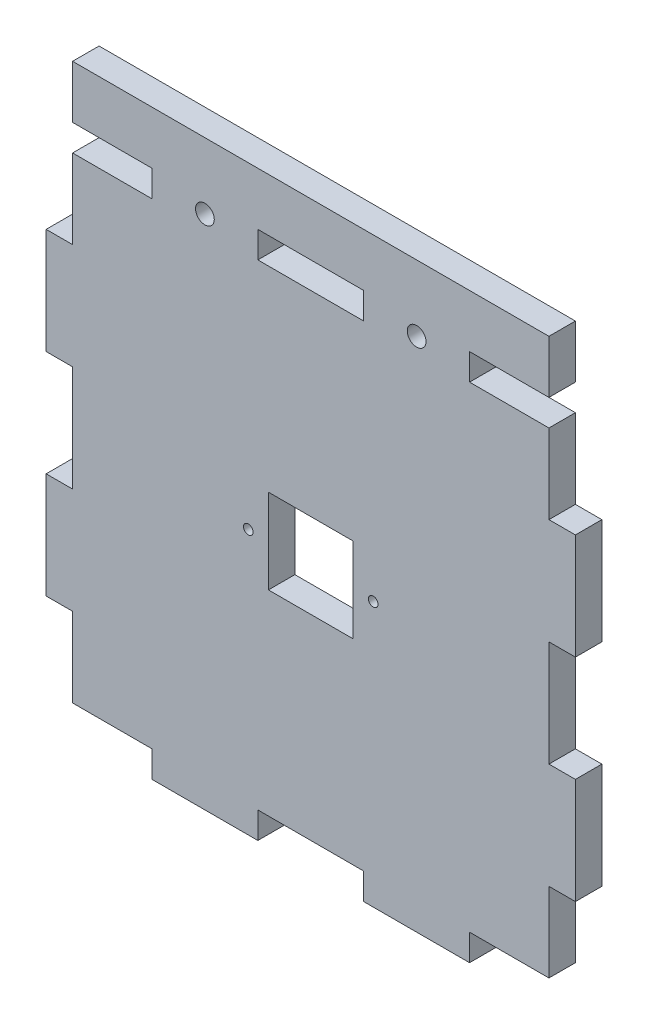
SolidWorks part; units mm, degrees
ref_plane "Front Plane" through (0, 0, 0) normal (0, 0, 1) x (1, 0, 0)
ref_plane "Top Plane" through (0, 0, 0) normal (0, 1, 0) x (1, 0, 0)
ref_plane "Right Plane" through (0, 0, 0) normal (1, 0, 0) x (0, 0, -1)
sketch "Sketch1" plane through (0, 0, 0) normal (0, 0, 1) x (1, 0, 0)
  line L1 (0, 0) -> (127, 0)
  line L2 (0, 0) -> (0, 139.7)
  line L3 (0, 139.7) -> (127, 139.7)
  line L4 (127, 0) -> (127, 139.7)
  dimension "D1" = 127
  dimension "D2" = 139.7
extrude "Boss-Extrude1" add sketch "Sketch1" along normal blind 6.35
sketch "Sketch5" plane through (0, 0, 6.35) normal (0, 0, 1) x (1, 0, 0)
  line L1 (0, 0) -> (6.35, 0)
  line L2 (0, 0) -> (0, 25.4)
  line L3 (0, 25.4) -> (6.35, 25.4)
  line L4 (6.35, 0) -> (6.35, 25.4)
  dimension "D1" = 25.4
  dimension "D2" = 6.35
extrude "Cut-Extrude4" cut sketch "Sketch5" against normal blind 6.35
sketch "Sketch6" plane through (0, 0, 6.35) normal (0, 0, 1) x (1, 0, 0)
  line L1 (0, 0) -> (25.4, 0)
  line L2 (0, 0) -> (0, 6.35)
  line L3 (0, 6.35) -> (25.4, 6.35)
  line L4 (25.4, 0) -> (25.4, 6.35)
  dimension "D1" = 6.35
  dimension "D2" = 25.4
extrude "Cut-Extrude5" cut sketch "Sketch6" against normal blind 6.35
pattern_linear "LPattern5" count 3 spacing 50.8 along (0, 1, 0) count 2 spacing 120.65 along (1, 0, 0) of "Cut-Extrude4"
pattern_linear "LPattern6" count 3 spacing 50.8 along (1, 0, 0) count 2 spacing 120.65 along (0, 1, 0) of "Cut-Extrude5"
sketch "Sketch7" plane through (0, 0, 6.35) normal (0, 0, 1) x (1, 0, 0)
  line L1 (6.35, 120.65) -> (0, 120.65)
  line L2 (6.35, 120.65) -> (6.35, 139.7)
  line L3 (6.35, 139.7) -> (0, 139.7)
  line L4 (0, 120.65) -> (0, 139.7)
  dimension "D1" = 6.35
  dimension "D2" = 19.05
extrude "Cut-Extrude6" cut sketch "Sketch7" against normal blind 6.35
sketch "Sketch12" plane through (0, 0, 6.35) normal (0, 0, 1) x (1, 0, 0)
  line L0 (127, 127) -> (127, 139.7) construction
  line L1 (127, 139.7) -> (120.65, 139.7)
  line L2 (127, 139.7) -> (127, 127)
  line L3 (127, 127) -> (120.65, 127)
  line L4 (120.65, 139.7) -> (120.65, 127)
  line L5 (127, 139.7) -> (6.35, 139.7) construction
  dimension "D1" = 6.35
  dimension "D2" = 12.7
extrude "Cut-Extrude9" cut sketch "Sketch12" against normal blind 7.62
hole_wizard "#8 Clearance Hole1" positions "Sketch10" profile "Sketch9" hole size "#8" standard "ANSI Inch"
sketch "Sketch10" plane through (0, 0, 6.35) normal (0, 0, 1) x (1, 0, 0)
  line L2 (25.4, 120.65) -> (25.4, 127) construction
  line L3 (76.2, 127) -> (50.8, 127) construction
  point P0 (38.1, 123.825)
  point P2 (88.9, 123.825)
  point P10 (25.4, 123.825)
  dimension "D1" = 12.7
  dimension "D3" = 12.7
  dimension "D4" = 3.175
sketch "Sketch9" plane through (38.1, 123.825, 6.35) normal (1, 0, 0) x (0, -1, 0)
  line L0 (0, 0) -> (0, 11.5107)
  line L1 (0, 11.5107) -> (2.2479, 10.16)
  line L2 (2.2479, 10.16) -> (2.2479, 0)
  line L5 (2.2479, 0) -> (0, 0)
  line L10 (0, 11.5107) -> (-2.2479, 10.16) construction
  line L11 (0, -6.35) -> (0, 107.95) construction
  dimension "Hole Dia." = 4.4958
  dimension "Hole Depth" = 10.16
  dimension "Drill Angle" = 118
sketch "Sketch11" plane through (0, 0, 6.35) normal (0, 0, 1) x (1, 0, 0)
  line L1 (53.34, 73.66) -> (73.66, 73.66)
  line L2 (53.34, 73.66) -> (53.34, 53.34)
  line L3 (53.34, 53.34) -> (73.66, 53.34)
  line L4 (73.66, 73.66) -> (73.66, 53.34)
  line L5 (120.65, 76.2) -> (120.65, 50.8) construction
  line L6 (0, 101.6) -> (0, 76.2) construction
  circle A0 centre (48.514, 63.5) radius 1.143
  circle A1 centre (78.486, 63.5) radius 1.143
  point P6 (63.5, 73.66)
  point P13 (73.66, 63.5)
  point P14 (53.34, 63.5)
  point P15 (120.65, 63.5)
  dimension "D5" = 2.286
  dimension "D6" = 2.286
  dimension "D7" = 14.986
  dimension "D8" = 14.986
  dimension "D1" = 0
  dimension "D2" = 20.32
  dimension "D3" = 20.32
  dimension "D4" = 63.5
extrude "Cut-Extrude8" cut sketch "Sketch11" against normal blind 7.62
